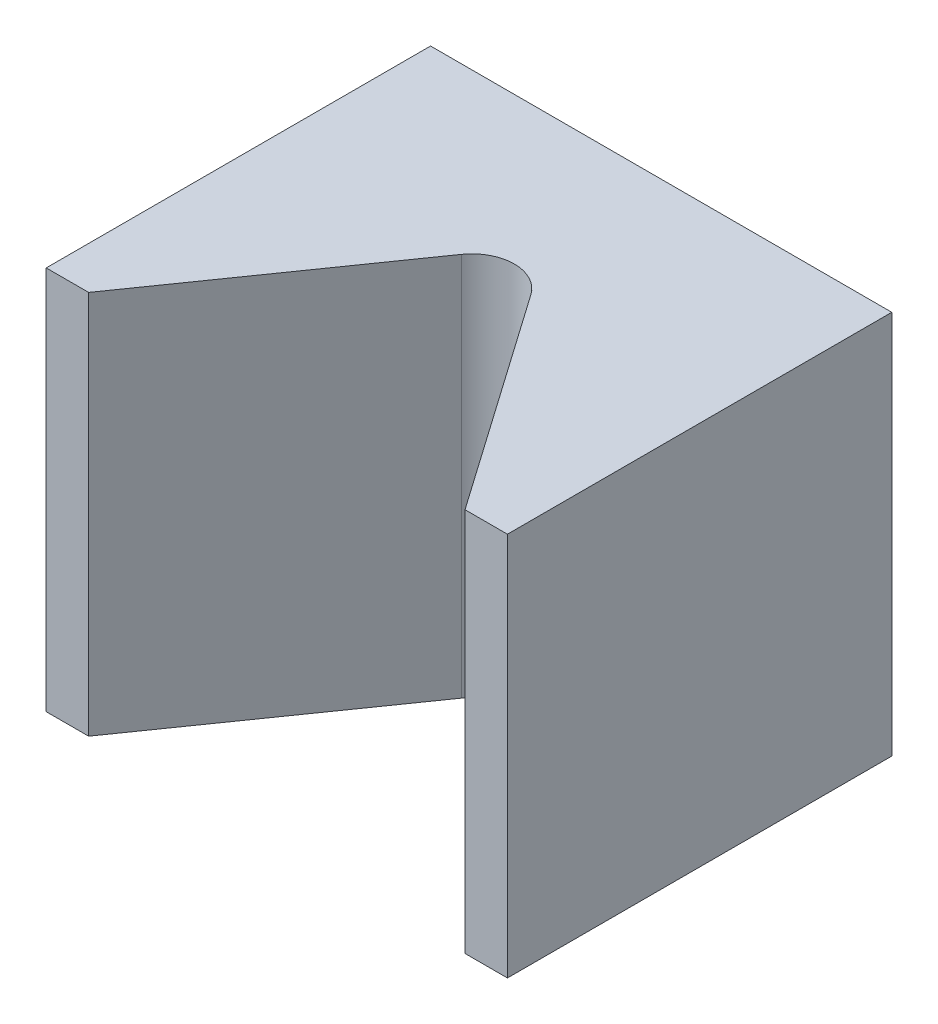
SolidWorks part; units mm, degrees
ref_plane "Front Plane" through (0, 0, 0) normal (0, 0, 1) x (1, 0, 0)
ref_plane "Top Plane" through (0, 0, 0) normal (0, 1, 0) x (1, 0, 0)
ref_plane "Right Plane" through (0, 0, 0) normal (1, 0, 0) x (0, 0, -1)
sketch "Sketch1" plane through (0, 0, 0) normal (0, 1, 0) x (1, 0, 0)
  line L0 (0.9046, 0.6327) -> (4.896, -5.0739)
  line L1 (4.896, -5.0739) -> (6, -5.0739)
  line L2 (6, -5.0739) -> (6, 4.9261)
  line L3 (6, 4.9261) -> (-6, 4.9261)
  line L4 (-6, 4.9261) -> (-6, -5.0739)
  line L5 (-6, -5.0739) -> (-4.896, -5.0739)
  line L6 (-4.896, -5.0739) -> (-0.9046, 0.6327)
  arc A0 (0.9046, 0.6327) -> (-0.9046, 0.6327) centre (0, 0) ccw
  point P9 (0, 0)
  dimension "D4" = 1.104
  dimension "D1" = 10
  dimension "D2" = 10
  dimension "D3" = 12
  dimension "D5" = 6.9639
  dimension "D6" = 6.9639
  dimension "D7" = 1.104
  dimension "D8" = 1.104
  dimension "D9" = 1.8093
  dimension "D10" = 55.03
extrude "Boss-Extrude1" add sketch "Sketch1" along normal blind 10
sketch "Sketch2" plane through (0, 0, -4.9261) normal (0, 0, -1) x (-1, 0, 0)
  line L0 (0, 0) -> (0, 10)
  line L1 (-6, 10) -> (6, 10) construction
  circle A0 centre (0, 5) radius 2.6
  dimension "D1" = 5.2
extrude "Cut-Extrude1" cut sketch "Sketch2" against normal blind 2 contours L0 A0 | L0 A0 region at (1.1035, 5, -4.9261) region at (-1.1035, 5, -4.9261)
